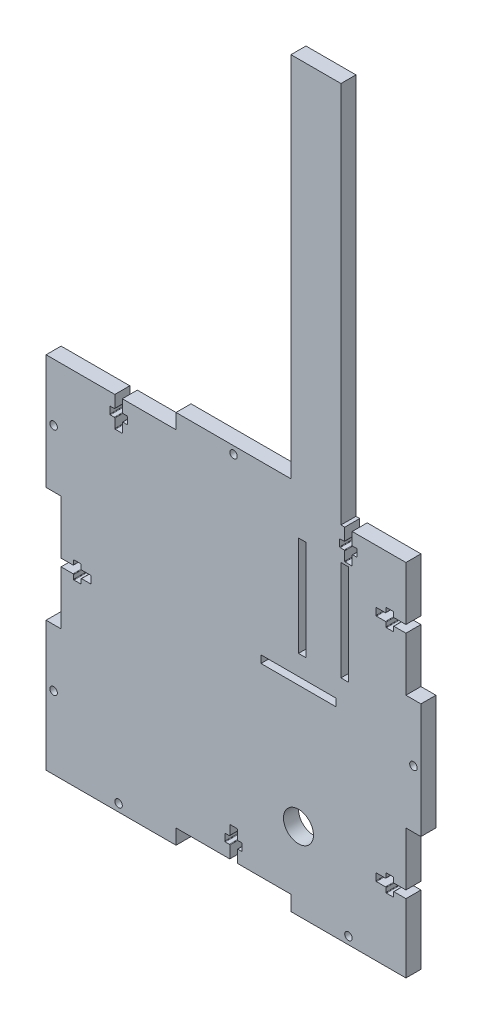
SolidWorks part; units mm, degrees
ref_plane "Front Plane" through (0, 0, 0) normal (0, 0, 1) x (1, 0, 0)
ref_plane "Top Plane" through (0, 0, 0) normal (0, 1, 0) x (1, 0, 0)
ref_plane "Right Plane" through (0, 0, 0) normal (1, 0, 0) x (0, 0, -1)
sketch "Sketch1" plane through (0, 0, 0) normal (0, 0, 1) x (1, 0, 0)
  line L0 (-69, 69) -> (-23, 69)
  line L5 (-75, -75) -> (75, -75) construction
  line L6 (-75, -75) -> (-75, 75) construction
  line L7 (-75, 75) -> (75, 75) construction
  line L8 (75, -75) -> (75, 75) construction
  line L9 (75, 23) -> (69, 23)
  line L10 (69, -23) -> (75, -23)
  line L11 (-69, -69) -> (69, -69) construction
  line L12 (-69, -69) -> (-69, 69) construction
  line L13 (-69, 69) -> (69, 69) construction
  line L14 (69, -69) -> (69, 69) construction
  line L15 (-69, -69) -> (69, 69) construction
  line L16 (69, -69) -> (69, -23)
  line L17 (-23, 69) -> (-23, 75)
  line L18 (-23, 75) -> (23, 75)
  line L19 (23, 75) -> (23, 69)
  line L20 (23, 69) -> (69, 69)
  line L21 (75, -23) -> (75, 23)
  line L22 (69, 23) -> (69, 69)
  line L23 (-75, 23) -> (-69, 23)
  line L24 (-69, 69) -> (-75, 69)
  line L25 (-75, 69) -> (-75, 23)
  line L26 (69, -69) -> (69, -75)
  line L27 (69, -75) -> (23, -75)
  line L28 (23, -75) -> (23, -69)
  line L29 (23, -69) -> (-23, -69)
  line L30 (-23, -69) -> (-23, -75)
  line L31 (-23, -75) -> (-69, -75)
  line L32 (-69, -75) -> (-69, -69) construction
  line L33 (-69, 23) -> (-69, -23)
  line L34 (-69, -23) -> (-75, -23)
  line L35 (-75, -23) -> (-75, -69)
  line L36 (-75, -69) -> (-69, -69) construction
  line L37 (-46, 69) -> (-46, -75) construction
  line L38 (-69, 69) -> (69, -69) construction
  line L39 (-75, -75) -> (-69, -75)
  line L40 (-75, -75) -> (-75, -69)
  point P0 (0, 0)
  point P6 (-7, -7)
  point P26 (0, -75)
  point P27 (-75, 0)
  dimension "D1" = 150
  dimension "D2" = 150
  dimension "D5" = 46
  dimension "D3" = 6
  dimension "D6" = 6
  dimension "D7" = 6
extrude "Box Side" add sketch "Sketch1" along normal blind 6
sketch "Sketch2" plane through (0, 0, 6) normal (0, 0, 1) x (1, 0, 0)
  line L0 (23, 72) -> (-23, 72) construction
  line L1 (23, 75) -> (23, 69) construction
  line L2 (-23, 69) -> (-23, 75) construction
  line L3 (-46, 69) -> (-46, -75) construction
  line L5 (0, 75) -> (0, 69) construction
  line L6 (-23, 75) -> (23, 75) construction
  line L7 (-69, 69) -> (69, 69) construction
  line L16 (-46, 69) -> (-46, -75) construction
  line L21 (0, -69) -> (0, 69) construction
  line L35 (-69, 69) -> (-23, 69) construction
  line L36 (-44.5, 69) -> (-44.5, 64.2)
  line L37 (-44.3, 64) -> (-42.7, 64)
  line L38 (-42.5, 63.8) -> (-42.5, 61.2)
  line L39 (-42.7, 61) -> (-44.3, 61)
  line L40 (-44.5, 60.8) -> (-44.5, 57.2)
  line L46 (-44.7, 57) -> (-47.3, 57)
  line L48 (-44.5, 69) -> (-47.5, 69)
  line L51 (-47.5, 60.8) -> (-47.5, 57.2)
  line L52 (-49.3, 61) -> (-47.7, 61)
  line L53 (-49.5, 63.8) -> (-49.5, 61.2)
  line L54 (-47.7, 64) -> (-49.3, 64)
  line L55 (-47.5, 69) -> (-47.5, 64.2)
  line L56 (47.5, 69) -> (47.5, 64.2)
  line L57 (47.7, 64) -> (49.3, 64)
  line L58 (49.5, 63.8) -> (49.5, 61.2)
  line L59 (49.3, 61) -> (47.7, 61)
  line L60 (47.5, 60.8) -> (47.5, 57.2)
  line L61 (44.5, 69) -> (47.5, 69)
  line L62 (44.7, 57) -> (47.3, 57)
  line L63 (44.5, 60.8) -> (44.5, 57.2)
  line L64 (42.7, 61) -> (44.3, 61)
  line L65 (42.5, 63.8) -> (42.5, 61.2)
  line L66 (44.3, 64) -> (42.7, 64)
  line L67 (44.5, 69) -> (44.5, 64.2)
  line L68 (-69, -69) -> (69, 69) construction
  line L69 (-69, -69) -> (69, 69) construction
  line L70 (75, 0) -> (69, 0) construction
  line L71 (72, 23) -> (72, -23) construction
  line L72 (69, 44.5) -> (64.2, 44.5)
  line L73 (64, 44.3) -> (64, 42.7)
  line L74 (63.8, 42.5) -> (61.2, 42.5)
  line L75 (61, 42.7) -> (61, 44.3)
  line L76 (60.8, 44.5) -> (57.2, 44.5)
  line L77 (57, 44.7) -> (57, 47.3)
  line L78 (69, 44.5) -> (69, 47.5)
  line L79 (60.8, 47.5) -> (57.2, 47.5)
  line L80 (61, 49.3) -> (61, 47.7)
  line L81 (63.8, 49.5) -> (61.2, 49.5)
  line L82 (64, 47.7) -> (64, 49.3)
  line L83 (69, 47.5) -> (64.2, 47.5)
  line L84 (69, -47.5) -> (64.2, -47.5)
  line L85 (64, -47.7) -> (64, -49.3)
  line L86 (63.8, -49.5) -> (61.2, -49.5)
  line L87 (61, -49.3) -> (61, -47.7)
  line L88 (60.8, -47.5) -> (57.2, -47.5)
  line L89 (69, -44.5) -> (69, -47.5)
  line L90 (57, -44.7) -> (57, -47.3)
  line L91 (60.8, -44.5) -> (57.2, -44.5)
  line L92 (61, -42.7) -> (61, -44.3)
  line L93 (63.8, -42.5) -> (61.2, -42.5)
  line L94 (64, -44.3) -> (64, -42.7)
  line L95 (69, -44.5) -> (64.2, -44.5)
  line L120 (-69, 69) -> (69, -69) construction
  line L121 (-69, 69) -> (69, -69) construction
  line L122 (-1.5, -69) -> (1.5, -69)
  line L123 (-23, -69) -> (23, -69) construction
  line L124 (1.5, -69) -> (1.5, -64.2)
  line L125 (1.7, -64) -> (3.3, -64)
  line L126 (3.5, -63.8) -> (3.5, -61.2)
  line L127 (3.3, -61) -> (1.7, -61)
  line L128 (1.5, -60.8) -> (1.5, -57.2)
  line L129 (1.3, -57) -> (-1.3, -57)
  line L130 (-1.5, -60.8) -> (-1.5, -57.2)
  line L131 (-3.3, -61) -> (-1.7, -61)
  line L132 (-3.5, -63.8) -> (-3.5, -61.2)
  line L133 (-1.7, -64) -> (-3.3, -64)
  line L134 (-1.5, -69) -> (-1.5, -64.2)
  line L135 (-69, -1.5) -> (-64.2, -1.5)
  line L136 (-64, -1.7) -> (-64, -3.3)
  line L137 (-63.8, -3.5) -> (-61.2, -3.5)
  line L138 (-61, -3.3) -> (-61, -1.7)
  line L139 (-60.8, -1.5) -> (-57.2, -1.5)
  line L140 (-57, 1.3) -> (-57, -1.3)
  line L141 (-60.8, 1.5) -> (-57.2, 1.5)
  line L142 (-61, 3.3) -> (-61, 1.7)
  line L143 (-63.8, 3.5) -> (-61.2, 3.5)
  line L144 (-64, 1.7) -> (-64, 3.3)
  line L145 (-69, 1.5) -> (-64.2, 1.5)
  line L146 (-69, -1.5) -> (-69, 1.5)
  line L147 (-69, -72) -> (-23, -72) construction
  line L148 (-23, 69) -> (-75, 69) construction
  line L149 (-23, -75) -> (-23, -69) construction
  line L150 (-69, -69) -> (-69, -75) construction
  line L151 (-75, -75) -> (-23, -75) construction
  circle A0 centre (0, 72) radius 1.5
  arc A1 (-44.5, 57.2) -> (-44.7, 57) centre (-44.7, 57.2) cw
  arc A2 (-44.3, 61) -> (-44.5, 60.8) centre (-44.3, 60.8) ccw
  arc A3 (-42.5, 61.2) -> (-42.7, 61) centre (-42.7, 61.2) cw
  arc A4 (-42.7, 64) -> (-42.5, 63.8) centre (-42.7, 63.8) cw
  arc A5 (-44.5, 64.2) -> (-44.3, 64) centre (-44.3, 64.2) ccw
  arc A6 (-47.5, 64.2) -> (-47.7, 64) centre (-47.7, 64.2) cw
  arc A7 (-49.3, 64) -> (-49.5, 63.8) centre (-49.3, 63.8) ccw
  arc A8 (-49.5, 61.2) -> (-49.3, 61) centre (-49.3, 61.2) ccw
  arc A9 (-47.7, 61) -> (-47.5, 60.8) centre (-47.7, 60.8) cw
  arc A10 (-47.5, 57.2) -> (-47.3, 57) centre (-47.3, 57.2) ccw
  arc A11 (47.5, 57.2) -> (47.3, 57) centre (47.3, 57.2) cw
  arc A12 (47.7, 61) -> (47.5, 60.8) centre (47.7, 60.8) ccw
  arc A13 (49.5, 61.2) -> (49.3, 61) centre (49.3, 61.2) cw
  arc A14 (49.3, 64) -> (49.5, 63.8) centre (49.3, 63.8) cw
  arc A15 (47.5, 64.2) -> (47.7, 64) centre (47.7, 64.2) ccw
  arc A16 (44.5, 64.2) -> (44.3, 64) centre (44.3, 64.2) cw
  arc A17 (42.7, 64) -> (42.5, 63.8) centre (42.7, 63.8) ccw
  arc A18 (42.5, 61.2) -> (42.7, 61) centre (42.7, 61.2) ccw
  arc A19 (44.3, 61) -> (44.5, 60.8) centre (44.3, 60.8) cw
  arc A20 (44.5, 57.2) -> (44.7, 57) centre (44.7, 57.2) ccw
  arc A21 (57.2, 44.5) -> (57, 44.7) centre (57.2, 44.7) cw
  arc A22 (61, 44.3) -> (60.8, 44.5) centre (60.8, 44.3) ccw
  arc A23 (61.2, 42.5) -> (61, 42.7) centre (61.2, 42.7) cw
  arc A24 (64, 42.7) -> (63.8, 42.5) centre (63.8, 42.7) cw
  arc A25 (64.2, 44.5) -> (64, 44.3) centre (64.2, 44.3) ccw
  arc A26 (64.2, 47.5) -> (64, 47.7) centre (64.2, 47.7) cw
  arc A27 (64, 49.3) -> (63.8, 49.5) centre (63.8, 49.3) ccw
  arc A28 (61.2, 49.5) -> (61, 49.3) centre (61.2, 49.3) ccw
  arc A29 (61, 47.7) -> (60.8, 47.5) centre (60.8, 47.7) cw
  arc A30 (57.2, 47.5) -> (57, 47.3) centre (57.2, 47.3) ccw
  arc A31 (57.2, -47.5) -> (57, -47.3) centre (57.2, -47.3) cw
  arc A32 (61, -47.7) -> (60.8, -47.5) centre (60.8, -47.7) ccw
  arc A33 (61.2, -49.5) -> (61, -49.3) centre (61.2, -49.3) cw
  arc A34 (64, -49.3) -> (63.8, -49.5) centre (63.8, -49.3) cw
  arc A35 (64.2, -47.5) -> (64, -47.7) centre (64.2, -47.7) ccw
  arc A36 (64.2, -44.5) -> (64, -44.3) centre (64.2, -44.3) cw
  arc A37 (64, -42.7) -> (63.8, -42.5) centre (63.8, -42.7) ccw
  arc A38 (61.2, -42.5) -> (61, -42.7) centre (61.2, -42.7) ccw
  arc A39 (61, -44.3) -> (60.8, -44.5) centre (60.8, -44.3) cw
  arc A40 (57.2, -44.5) -> (57, -44.7) centre (57.2, -44.7) ccw
  circle A41 centre (72, 0) radius 1.5
  arc A62 (1.5, -57.2) -> (1.3, -57) centre (1.3, -57.2) ccw
  arc A63 (1.7, -61) -> (1.5, -60.8) centre (1.7, -60.8) cw
  arc A64 (3.5, -61.2) -> (3.3, -61) centre (3.3, -61.2) ccw
  arc A65 (3.3, -64) -> (3.5, -63.8) centre (3.3, -63.8) ccw
  arc A66 (1.5, -64.2) -> (1.7, -64) centre (1.7, -64.2) cw
  arc A67 (-1.5, -64.2) -> (-1.7, -64) centre (-1.7, -64.2) ccw
  arc A68 (-3.3, -64) -> (-3.5, -63.8) centre (-3.3, -63.8) cw
  arc A69 (-3.5, -61.2) -> (-3.3, -61) centre (-3.3, -61.2) cw
  arc A70 (-1.7, -61) -> (-1.5, -60.8) centre (-1.7, -60.8) ccw
  arc A71 (-1.5, -57.2) -> (-1.3, -57) centre (-1.3, -57.2) cw
  arc A72 (-57.2, -1.5) -> (-57, -1.3) centre (-57.2, -1.3) ccw
  arc A73 (-61, -1.7) -> (-60.8, -1.5) centre (-60.8, -1.7) cw
  arc A74 (-61.2, -3.5) -> (-61, -3.3) centre (-61.2, -3.3) ccw
  arc A75 (-64, -3.3) -> (-63.8, -3.5) centre (-63.8, -3.3) ccw
  arc A76 (-64.2, -1.5) -> (-64, -1.7) centre (-64.2, -1.7) cw
  arc A77 (-64.2, 1.5) -> (-64, 1.7) centre (-64.2, 1.7) ccw
  arc A78 (-64, 3.3) -> (-63.8, 3.5) centre (-63.8, 3.3) cw
  arc A79 (-61.2, 3.5) -> (-61, 3.3) centre (-61.2, 3.3) cw
  arc A80 (-61, 1.7) -> (-60.8, 1.5) centre (-60.8, 1.7) ccw
  arc A81 (-57.2, 1.5) -> (-57, 1.3) centre (-57.2, 1.3) cw
  circle A82 centre (-46, -72) radius 1.5
  circle A83 centre (46, -72) radius 1.5
  circle A84 centre (-72, 46) radius 1.5
  circle A85 centre (-72, -46) radius 1.5
  point P6 (0, 72)
  point P38 (0, 0)
  point P56 (-46, 57)
  point P88 (46, 57)
  point P161 (57, 46)
  point P162 (57, -46)
  point P198 (0, -57)
  point P231 (-57, 0)
  point P234 (-42.5, 62.5)
  dimension "D1" = 3
  dimension "D2" = 0.2
  dimension "D8" = 0.2
  dimension "D14" = 3
  dimension "D4" = 3
  dimension "D7" = 1.5
  dimension "D10" = 3
  dimension "D12" = 1.5
  dimension "D9" = 12
  dimension "D11" = 5
  dimension "D13" = 7
  dimension "D3" = 12
  dimension "D5" = 7
  dimension "D6" = 5
extrude "Screw Cut-outs" cut sketch "Sketch2" against normal through all
sketch "Bearing Hole" plane through (0, 0, 6) normal (0, 0, 1) x (1, 0, 0)
  line L0 (20, -69) -> (50020, -69) construction
  line L1 (69, -44.5) -> (69, -23) construction
  line L4 (26, -41) -> (50026, -41) construction
  line L5 (26.5774, -47) -> (50026.5774, -47) construction
  line L8 (29, -52) -> (29, -50052) construction
  circle A0 centre (26, -44) radius 3 construction
  circle A1 centre (26, -54) radius 15 construction
  circle A2 centre (26, -44) radius 6
  dimension "D2" = 6
  dimension "D4" = 30
  dimension "D5" = 12
  dimension "D1" = 7
  dimension "D3" = 43
extrude "Shaft Hole" cut sketch "Bearing Hole" against normal through all
sketch "Sketch4" plane through (0, 0, 0) normal (0, 0, -1) x (-1, 0, 0)
  line L0 (-72, 1.5) -> (49928, 1.5) construction
  line L1 (-41, 8) -> (-11, 8)
  line L2 (-41, 8) -> (-41, 5)
  line L3 (-41, 5) -> (-11, 5)
  line L4 (-11, 8) -> (-11, 5)
  line L5 (-75, -23) -> (-75, 23) construction
  line L6 (-69, 23) -> (-69, 44.5) construction
  line L7 (-46, 56) -> (-43, 56)
  line L8 (-46, 56) -> (-46, 16)
  line L9 (-46, 16) -> (-43, 16)
  line L10 (-43, 56) -> (-43, 16)
  line L11 (-29, 56) -> (-26, 56)
  line L12 (-29, 56) -> (-29, 16)
  line L13 (-29, 16) -> (-26, 16)
  line L14 (-26, 56) -> (-26, 16)
  line L15 (-44.5, 69) -> (-23, 69) construction
  circle A1 centre (-72, 0) radius 1.5 construction
  point P18 (-29, 36)
  dimension "D1" = 3.5
  dimension "D2" = 30
  dimension "D3" = 3
  dimension "D4" = 34
  dimension "D5" = 14
  dimension "D6" = 23
  dimension "D7" = 13
  dimension "D8" = 3
  dimension "D9" = 40
extrude "Grooves" cut sketch "Sketch4" against normal up to surface (6 mm away) up to face at (32, -44, 6)
sketch "Sketch5" plane through (0, 69, 0) normal (0, 1, 0) x (1, 0, 0)
  line L0 (69, 0) -> (47.5, 0) construction
  line L1 (23, -6) -> (43, -6)
  line L2 (23, -6) -> (23, 0)
  line L3 (23, 0) -> (43, 0)
  line L4 (43, -6) -> (43, 0)
  line L5 (75, -6) -> (75, 0) construction
  dimension "D1" = 32
extrude "Boss-Extrude1" add sketch "Sketch5" along normal blind 153
equation "\"filletRadius\"=0.2"
equation "\"D8@Sketch2\"=\"filletRadius\""
equation "\"D2@Sketch2\"=\"filletRadius\""
equation "\"fingerWidth\"= 46"
equation "\"D5@Sketch1\"=\"fingerWidth\""
equation "\"wallThickness\"= 6"
equation "\"D3@Sketch1\" = \"wallThickness\""
equation "\"D6@Sketch1\" = \"wallThickness\""
equation "\"D7@Sketch1\" = \"wallThickness\""
equation "\"D1@Box Side\" = \"wallThickness\""
equation "\"M3\"= 3"
equation "\"D14@Sketch2\"=\"M3\""
equation "\"D1@Sketch2\"=\"M3\""
equation "\"D12@Sketch2\"=\"M3\"/2"
equation "\"nutThickness\"=3"
equation "\"D10@Sketch2\" = \"nutThickness\""
equation "\"boltLength\"= 12"
equation "\"D9@Sketch2\" = \"boltLength\""
equation "\"distanceToNut\"= 5"
equation "\"D11@Sketch2\" = \"distanceToNut\""
equation "\"D13@Sketch2\" = \"nutWidth\""
equation "\"D7@Sketch2\"=\"M3\"/2"
equation "\"D4@Sketch2\" = \"nutThickness\""
equation "\"D3@Sketch2\" = \"boltLength\""
equation "\"D5@Sketch2\" = \"nutWidth\""
equation "\"D6@Sketch2\" = \"distanceToNut\""
equation "\"sideLength\"=150"
equation "\"D1@Sketch1\"=\"sideLength\""
equation "\"D2@Sketch1\"=\"sideLength\""
equation "\"nutWidth\"=7"
